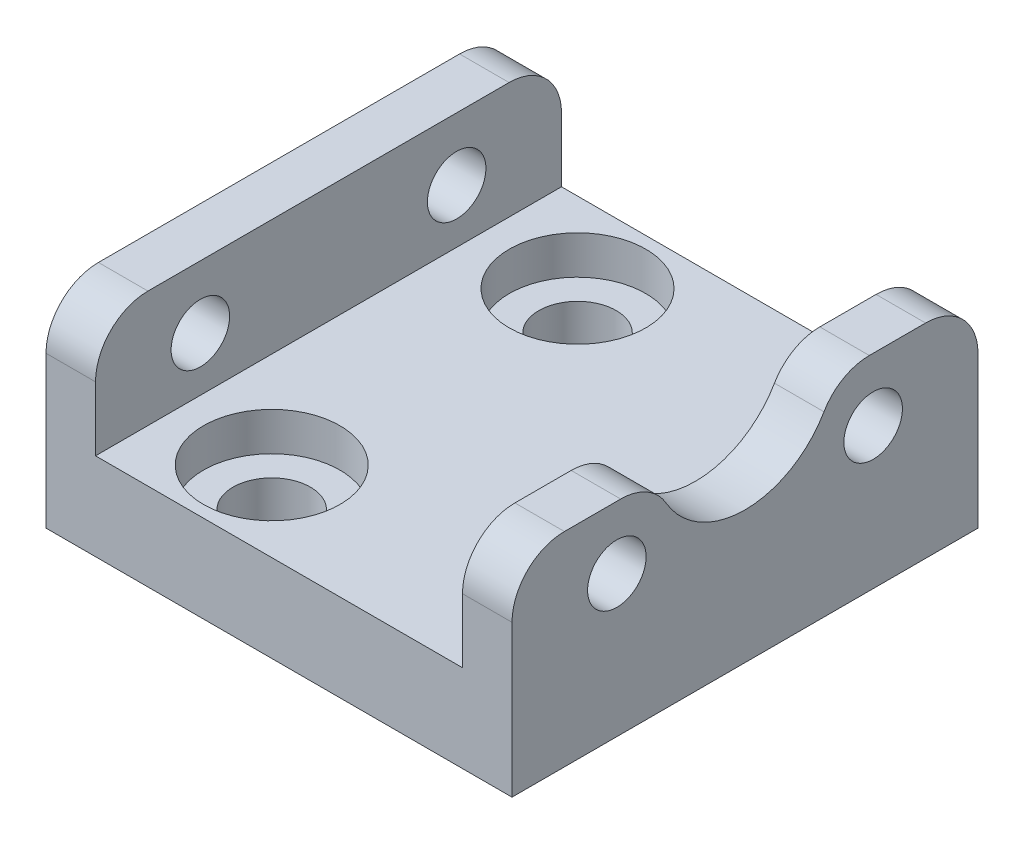
SolidWorks part; units mm, degrees
material "ABS"
ref_plane "Front" through (0, 0, 0) normal (0, 0, 1) x (1, 0, 0)
ref_plane "Top" through (0, 0, 0) normal (0, 1, 0) x (1, 0, 0)
ref_plane "Right" through (0, 0, 0) normal (1, 0, 0) x (0, 0, -1)
ref_axis "Axis1" through (0, 0, 55) along (0, 0, -1)
sketch "Sketch1" plane through (0, 0, 0) normal (0, 1, 0) x (1, 0, 0)
  line L1 (0, 0) -> (40.64, 0)
  line L2 (0, 0) -> (0, -40.64)
  line L3 (0, -40.64) -> (40.64, -40.64)
  line L4 (40.64, 0) -> (40.64, -40.64)
  line L5 (0, 0) -> (40.64, -40.64) construction
  line L6 (0, -40.64) -> (40.64, 0) construction
  point P4 (20.32, -20.32)
  dimension "D1" = 40.64
  dimension "D2" = 40.64
extrude "Boss-Extrude1" add sketch "Sketch1" along normal blind 7.62
sketch "Sketch2" plane through (0, 7.62, 0) normal (0, 1, 0) x (1, 0, 0)
  line L0 (0, -40.64) -> (40.64, -40.64) construction
  line L1 (0, 0) -> (4.318, 0)
  line L2 (0, 0) -> (0, -40.64)
  line L3 (0, -40.64) -> (4.318, -40.64)
  line L4 (4.318, 0) -> (4.318, -40.64)
  line L5 (0, 0) -> (4.318, -40.64) construction
  line L6 (0, -40.64) -> (4.318, 0) construction
  line L7 (40.64, 0) -> (0, 0) construction
  line L8 (36.322, 0) -> (40.64, 0)
  line L9 (36.322, 0) -> (36.322, -40.64)
  line L10 (36.322, -40.64) -> (40.64, -40.64)
  line L11 (40.64, 0) -> (40.64, -40.64)
  line L12 (36.322, 0) -> (40.64, -40.64) construction
  line L13 (36.322, -40.64) -> (40.64, 0) construction
  point P4 (2.159, -20.32)
  point P12 (38.481, -20.32)
  dimension "D1" = 32.004
extrude "Boss-Extrude2" add sketch "Sketch2" along normal blind 10.16
hole_wizard "#10 Clearance Hole1" positions "Sketch4" profile "Sketch5" hole size "#10" standard "ANSI Inch" end condition through all
sketch "Sketch4" plane through (0, 0, 0) normal (-1, 0, 0) x (0, 0, 1)
  line L0 (0, 12.319) -> (40.64, 12.319) construction
  line L1 (0, 17.78) -> (0, 0) construction
  line L2 (40.64, 17.78) -> (40.64, 0) construction
  point P0 (9.144, 12.319)
  point P2 (31.496, 12.319)
  dimension "D1" = 31.496
sketch "Sketch5" plane through (0, 12.319, 9.144) normal (0, 1, 0) x (0, 0, 1)
  line L0 (0, 0) -> (0, 40.64)
  line L1 (0, 40.64) -> (2.5527, 40.64)
  line L2 (2.5527, 40.64) -> (2.5527, 0)
  line L5 (2.5527, 0) -> (0, 0)
  line L11 (0, -6.35) -> (0, 107.95) construction
  dimension "Thru Hole Dia." = 5.1054
  dimension "Thru Hole Depth" = 40.64
hole_wizard "CBORE for 1/4 Button Head Cap Screw1" positions "Sketch6" profile "Sketch7" counterbore size "1/4" standard "ANSI Inch" end condition through all
sketch "Sketch6" plane through (0, 7.62, 0) normal (0, 1, 0) x (1, 0, 0)
  line L0 (36.322, -20.32) -> (4.318, -20.32) construction
  line L1 (36.322, 0) -> (36.322, -40.64) construction
  line L2 (4.318, -40.64) -> (4.318, 0) construction
  line L4 (12.7, -6.985) -> (12.7, -33.655) construction
  point P0 (12.7, -6.985)
  point P2 (12.7, -33.655)
  dimension "D1" = 8.382
  dimension "D2" = 26.67
sketch "Sketch7" plane through (12.7, 7.62, 6.985) normal (1, 0, 0) x (0, 0, 1)
  line L0 (0, 0) -> (0, 7.62)
  line L1 (0, 7.62) -> (3.3782, 7.62)
  line L3 (3.3782, 7.62) -> (3.3782, 3.3528)
  line L4 (3.3782, 3.3528) -> (5.9538, 3.3528)
  line L5 (5.9538, 3.3528) -> (5.9538, 0)
  line L7 (5.9538, 0) -> (0, 0)
  line L11 (0, -6.35) -> (0, 107.95) construction
  dimension "Thru Hole Dia." = 6.7564
  dimension "Thru Hole Depth" = 7.62
  dimension "C'Bore Dia." = 11.9075
  dimension "C'Bore Depth" = 3.3528
sketch "Sketch8" plane through (40.64, 0, 0) normal (1, 0, 0) x (0, 0, -1)
  line L0 (-20.32, 0) -> (-20.32, 19.5046) construction
  line L1 (-40.64, 0) -> (0, 0) construction
  circle A0 centre (-20.32, 19.5046) radius 7.9654
  dimension "D1" = 15.9307
  dimension "D2" = 19.5046
extrude "Cut-Extrude1" cut sketch "Sketch8" against normal up to next
fillet "Fillet1" radius 4.572 6 edges at (38.481, 17.78, 28.0964) (38.481, 17.78, 12.5436) (38.481, 17.78, 0) (38.481, 17.78, 40.64) (2.159, 17.78, 0) (2.159, 17.78, 40.64)
sketch "tab_geometry" [suppressed] plane through (0, 0, 0) normal (0, -1, 0) x (1, 0, 0)
  line L0 (12.7, -2.159) -> (12.7, 16.129) construction
  line L1 (8.89, -2.159) -> (8.89, 16.129)
  line L2 (16.51, -2.159) -> (16.51, 16.129)
  line L3 (4.5797, -5.969) -> (16.51, -5.969) construction
  line L4 (16.51, -5.969) -> (16.51, 19.939) construction
  line L5 (16.51, 19.939) -> (4.5797, 19.939) construction
  line L6 (4.5797, 19.939) -> (4.5797, -5.969) construction
  line L7 (0, 20.32) -> (40.64, 20.32) construction
  line L8 (0, 0) -> (0, 40.64) construction
  line L9 (40.64, 40.64) -> (40.64, 0) construction
  line L10 (12.7, 42.799) -> (12.7, 24.511) construction
  line L11 (8.89, 42.799) -> (8.89, 24.511)
  line L12 (16.51, 42.799) -> (16.51, 24.511)
  arc A0 (8.89, -2.159) -> (16.51, -2.159) centre (12.7, -2.159) ccw
  arc A1 (16.51, 16.129) -> (8.89, 16.129) centre (12.7, 16.129) ccw
  arc A2 (8.89, 42.799) -> (16.51, 42.799) centre (12.7, 42.799) cw
  arc A3 (16.51, 24.511) -> (8.89, 24.511) centre (12.7, 24.511) cw
  point P2 (12.7, 6.985)
  point P20 (12.7, 33.655)
  dimension "D1" = 25.908
  dimension "D2" = 7.62
